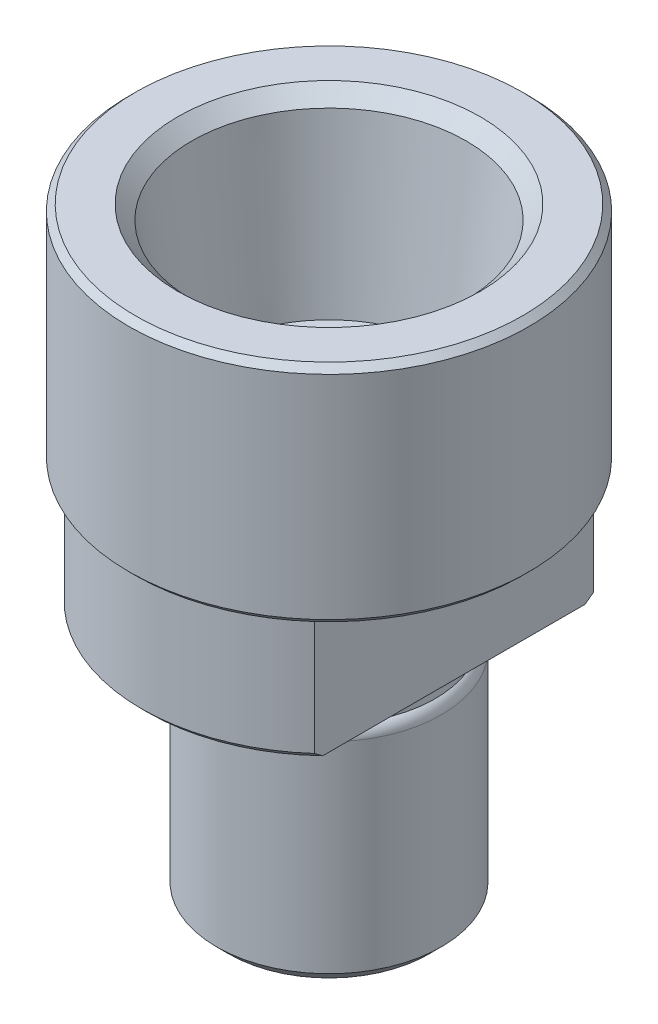
SolidWorks part; units mm, degrees
ref_plane "Alzado" through (0, 0, 0) normal (0, 0, 1) x (1, 0, 0)
ref_plane "Planta" through (0, 0, 0) normal (0, 1, 0) x (1, 0, 0)
ref_plane "Vista lateral" through (0, 0, 0) normal (1, 0, 0) x (0, 0, -1)
sketch "Croquis1" plane through (0, 0, 0) normal (0, 0, 1) x (1, 0, 0)
  line L0 (0, 50.375) -> (0, -55.9379) construction
  line L1 (11.11, 48) -> (16, 48)
  line L2 (16, 48) -> (16, 30)
  line L3 (16, 30) -> (15, 30)
  line L4 (15, 30) -> (15, 20)
  line L5 (15, 20) -> (8.5, 20)
  line L6 (9, 17.9517) -> (9, 0)
  line L7 (9, 0) -> (4.7625, 0)
  line L8 (4.7625, 0) -> (4.7625, 32.2412)
  line L9 (4.7625, 32.2412) -> (5.7625, 33.2412)
  line L10 (11.11, 48) -> (9.525, 33.2412)
  line L11 (9.525, 33.2412) -> (5.7625, 33.2412)
  line L12 (8.5, 20) -> (8.5, 17.9517)
  line L13 (8.5, 17.9517) -> (9, 17.9517)
  dimension "D1" = 18
  dimension "D2" = 10
  dimension "D3" = 30
  dimension "D4" = 4.7625
  dimension "D5" = 9
  dimension "D6" = 11.11
  dimension "D7" = 9.525
  dimension "D8" = 1
  dimension "D9" = 1
  dimension "D10" = 15
  dimension "D12" = 8.5
  dimension "D13" = 16
revolve "Revolución1" add sketch "Croquis1" angle 360 about L0
chamfer "Chaflán1" distance 1 angle 45 1 edges at (0, 0, 9)
fillet "Redondeo1" radius 1 1 edges at (0, 17.9517, 9)
chamfer "Chaflán2" distance 0.5 angle 45 3 edges at (0, 48, 16) (0, 30, 16) (0, 20, 15)
sketch "Croquis3" plane through (0, 0, 0) normal (0, -1, 0) x (1, 0, 0)
  line L0 (0, 18.5909) -> (0, -22.1588) construction
  line L1 (10, 11.1803) -> (10, -11.1803)
  line L2 (-10, 11.1803) -> (-10, -11.1803)
  line L3 (10, 11.1803) -> (24.8279, 11.1803)
  line L4 (24.8279, 11.1803) -> (24.246, -11.1803)
  line L5 (24.246, -11.1803) -> (10, -11.1803)
  line L6 (-10, 11.1803) -> (-24.7309, 11.1803)
  line L7 (-24.7309, 11.1803) -> (-24.7309, -11.1803)
  line L8 (-24.7309, -11.1803) -> (-10, -11.1803)
  circle A0 centre (0, 0) radius 15 construction
  circle A1 centre (0, 0) radius 15 construction
  dimension "D1" = 10
  dimension "D2" = 10
extrude "Cortar-Extruir1" cut sketch "Croquis3" against normal up to surface (30 mm away) up to face at (0, 30, 15.5)
chamfer "Chaflán3" distance 1 angle 45 1 edges at (0, 48, 11.11) first distance on face at (0, 48, -15.5)
